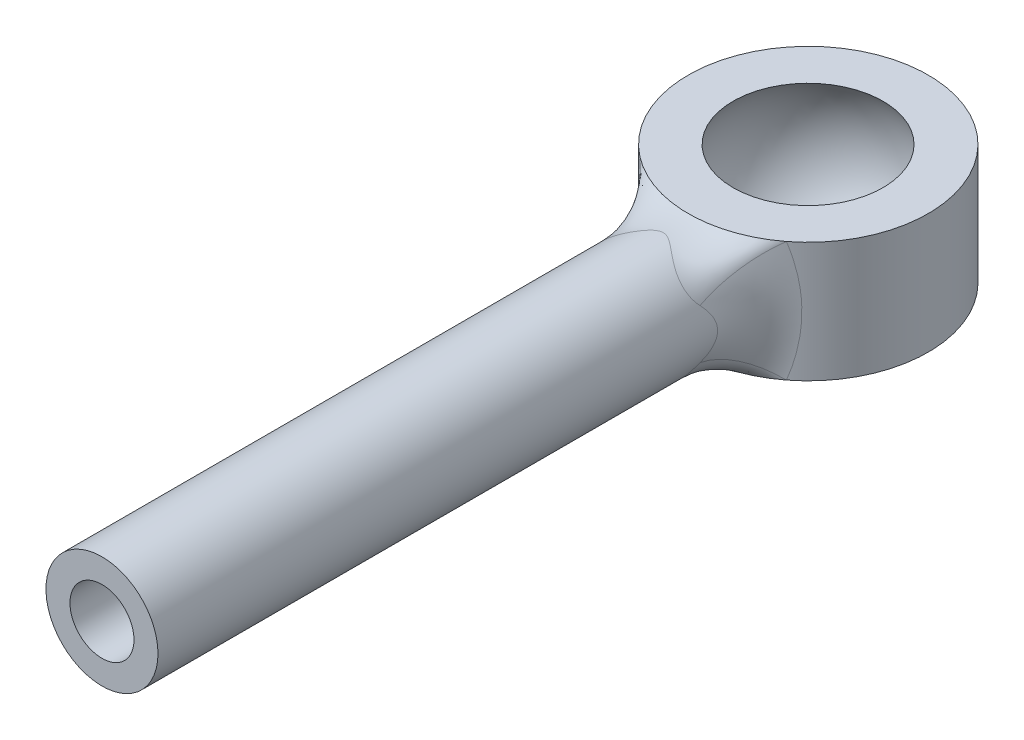
SolidWorks part; units mm, degrees
ref_plane "Front Plane" through (0, 0, 0) normal (0, 0, 1) x (1, 0, 0)
ref_plane "Top Plane" through (0, 0, 0) normal (0, 1, 0) x (1, 0, 0)
ref_plane "Right Plane" through (0, 0, 0) normal (1, 0, 0) x (0, 0, -1)
sketch "Sketch1" plane through (0, 0, 0) normal (0, 0, 1) x (1, 0, 0)
  circle A0 centre (0, 0) radius 4
  circle A1 centre (0, 0) radius 7
  dimension "D2" = 8
extrude "Boss-Extrude1" add sketch "Sketch1" along normal blind 75
sketch "Sketch2" plane through (0, 0, 0) normal (0, 1, 0) x (1, 0, 0)
  line L0 (0, 0) -> (0, 13.2665)
  line L1 (7, 0) -> (-7, 0) construction
  circle A0 centre (0, 13.2665) radius 15
  circle A1 centre (0, 13.2665) radius 12.5
  dimension "D2" = 30
  dimension "D3" = 2.5
  dimension "D1" = 13.2665
extrude "Boss-Extrude2" add sketch "Sketch2" along normal mid plane 15 contours A0 A1 region at (-14.5757, 0, -13.2665)
fillet "Fillet1" radius 10 1 edges at (6.9488, -0.8454, 0.0269)
sketch "Sketch3" plane through (0, 0, 0) normal (0, 0, 1) x (1, 0, 0)
  circle A0 centre (0, 0) radius 6
extrude "Boss-Extrude3" add sketch "Sketch3" against normal blind 5 from offset 5
sketch "Sketch5" plane through (0, 0, 0) normal (0, 1, 0) x (1, 0, 0)
  circle A0 centre (0, 13.2665) radius 12.5
extrude "Boss-Extrude4" add sketch "Sketch5" along normal through all and the other way through all
sketch "Sketch6" plane through (0, 0, 0) normal (0, 1, 0) x (1, 0, 0)
  circle A0 centre (0, 13.2665) radius 8.5
  dimension "D1" = 17
extrude "Cut-Extrude1" cut sketch "Sketch6" against normal through all both and the other way through all
sketch "Sketch7" plane through (0, 0, 0) normal (1, 0, 0) x (0, 0, -1)
  line L0 (28.2665, 0) -> (13.24, 0)
  line L1 (28.2665, -7.5) -> (28.2665, 7.5) construction
  line L2 (13.24, 0) -> (13.24, 12)
  line L3 (13.24, 0) -> (13.24, -12)
  arc A0 (13.24, -12) -> (13.24, 12) centre (13.24, 0) cw
  dimension "D1" = 15.0265
  dimension "D2" = 12
  dimension "D3" = 12
revolve "Cut-Revolve1" cut sketch "Sketch7" angle 360 about L2
